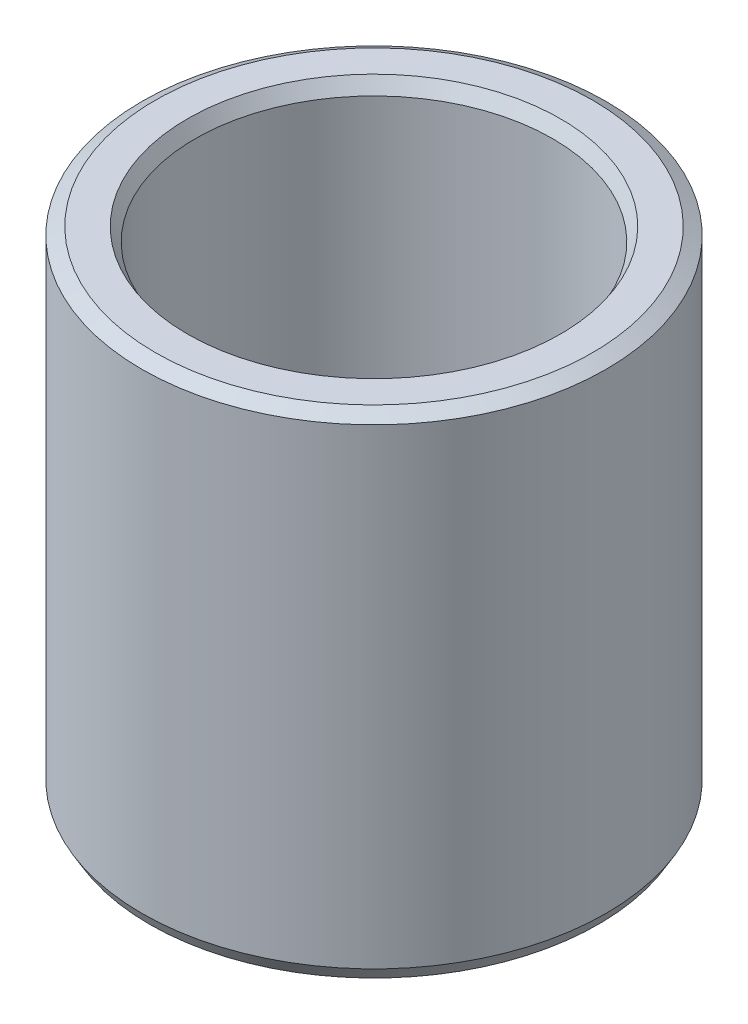
SolidWorks part; units mm, degrees
ref_plane "Front Plane" through (0, 0, 0) normal (0, 0, 1) x (1, 0, 0)
ref_plane "Top Plane" through (0, 0, 0) normal (0, 1, 0) x (1, 0, 0)
ref_plane "Right Plane" through (0, 0, 0) normal (1, 0, 0) x (0, 0, -1)
sketch "Sketch1" plane through (0, 0, 0) normal (0, 1, 0) x (1, 0, 0)
  circle A0 centre (0, 0) radius 35
  dimension "SLEEVE_OD" = 70
extrude "Boss-Extrude1" add sketch "Sketch1" along normal blind 74.2503
sketch "Sketch2" plane through (0, 0, 0) normal (0, 1, 0) x (1, 0, 0)
  circle A0 centre (0, 0) radius 26.9622
  dimension "BORE_D" = 53.9245
extrude "Cut-Extrude1" cut sketch "Sketch2" along normal through all
chamfer "Chamfer1" distance 1.1679 angle 60 4 edges at (0, 74.2503, 26.9622) (0, 0, 26.9622) (0, 0, 35) (0, 74.2503, 35) first distance on face at (0, 74.2503, 26.9622) first distance on face at (0, 0, 26.9622) first distance on face at (0, 74.2503, 35)
